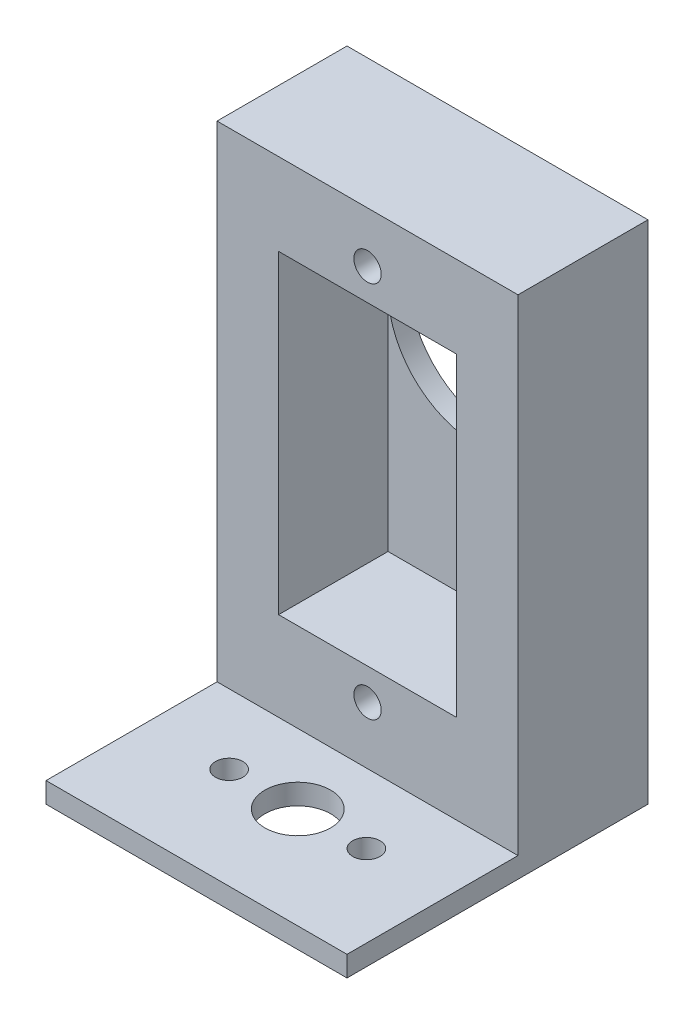
SolidWorks part; units mm, degrees
ref_plane "Front Plane" through (0, 0, 0) normal (0, 0, 1) x (1, 0, 0)
ref_plane "Top Plane" through (0, 0, 0) normal (0, 1, 0) x (1, 0, 0)
ref_plane "Right Plane" through (0, 0, 0) normal (1, 0, 0) x (0, 0, -1)
sketch "Sketch1" plane through (0, 0, 0) normal (0, 1, 0) x (1, 0, 0)
  line L1 (-11, -11) -> (11, -11)
  line L2 (-11, -11) -> (-11, 11)
  line L3 (-11, 11) -> (11, 11)
  line L4 (11, -11) -> (11, 11)
  line L5 (-11, -11) -> (11, 11) construction
  line L6 (-11, 11) -> (11, -11) construction
  point P0 (0, 0)
  dimension "D1" = 22
  dimension "D2" = 22
extrude "Boss-Extrude1" add sketch "Sketch1" along normal blind 37
sketch "Sketch3" plane through (11, 0, 0) normal (1, 0, 0) x (0, 0, -1)
  line L3 (11, 37) -> (8.5, 37)
  line L4 (11, 37) -> (11, 19)
  line L5 (11, 19) -> (8.5, 19)
  line L6 (8.5, 37) -> (8.5, 19)
  line L7 (-11, 37) -> (1.5, 46)
  line L8 (-11, 37) -> (-11, 1.5)
  line L9 (-11, 1.5) -> (1.5, 1.5)
  line L10 (1.5, 46) -> (1.5, 1.5)
  line M11 (11, 37) -> (-11, 37)
  line M12 (-11, 37) -> (-11, 0)
  dimension "D3" = 2.5
  dimension "D4" = 18
extrude "Cut-Extrude2" cut sketch "Sketch3" against normal through all contours L10 L9 M11 M12 region at (11, 19.25, 4.75)
sketch "Sketch9" plane through (0, 0, -1.5) normal (0, 0, 1) x (1, 0, 0)
  line L0 (-11, 1.5) -> (11, 1.5) construction
  line L1 (-6.5, 8) -> (6.5, 8)
  line L2 (-6.5, 8) -> (-6.5, 31)
  line L3 (-6.5, 31) -> (6.5, 31)
  line L4 (6.5, 8) -> (6.5, 31)
  line L5 (-6.5, 8) -> (6.5, 31) construction
  line L6 (-6.5, 31) -> (6.5, 8) construction
  point P0 (0, 19.5)
  dimension "D1" = 13
  dimension "D2" = 23
  dimension "D3" = 6.5
sketch "Sketch18" plane through (0, 1.5, 0) normal (0, 1, 0) x (1, 0, 0)
  circle A0 centre (0, -3.5999) radius 2.4
  circle A1 centre (5.0159, -3.5999) radius 1
  circle A2 centre (-5.0159, -3.5999) radius 1
extrude "Cut-Extrude10" cut sketch "Sketch18" against normal through all
extrude "Cut-Extrude4" cut sketch "Sketch9" against normal blind 8
sketch "Sketch10" plane through (0, 0, -9.5) normal (0, 0, 1) x (1, 0, 0)
  line L1 (6.5, 31) -> (-6.5, 31) construction
  circle A0 centre (0, 24.5) radius 6.5
  dimension "D1" = 13
  dimension "D2" = 6.5
extrude "Cut-Extrude5" cut sketch "Sketch10" against normal through all
sketch "Sketch11" plane through (0, 0, -1.5) normal (0, 0, 1) x (1, 0, 0)
  line L1 (6.5, 31) -> (0, 31) construction
  circle A0 centre (0, 33.3) radius 1
  circle A1 centre (0, 5.7) radius 1
  dimension "D1" = 27.6
  dimension "D2" = 2
  dimension "D3" = 2
  dimension "D4" = 2.3
extrude "Cut-Extrude6" cut sketch "Sketch11" against normal blind 8
